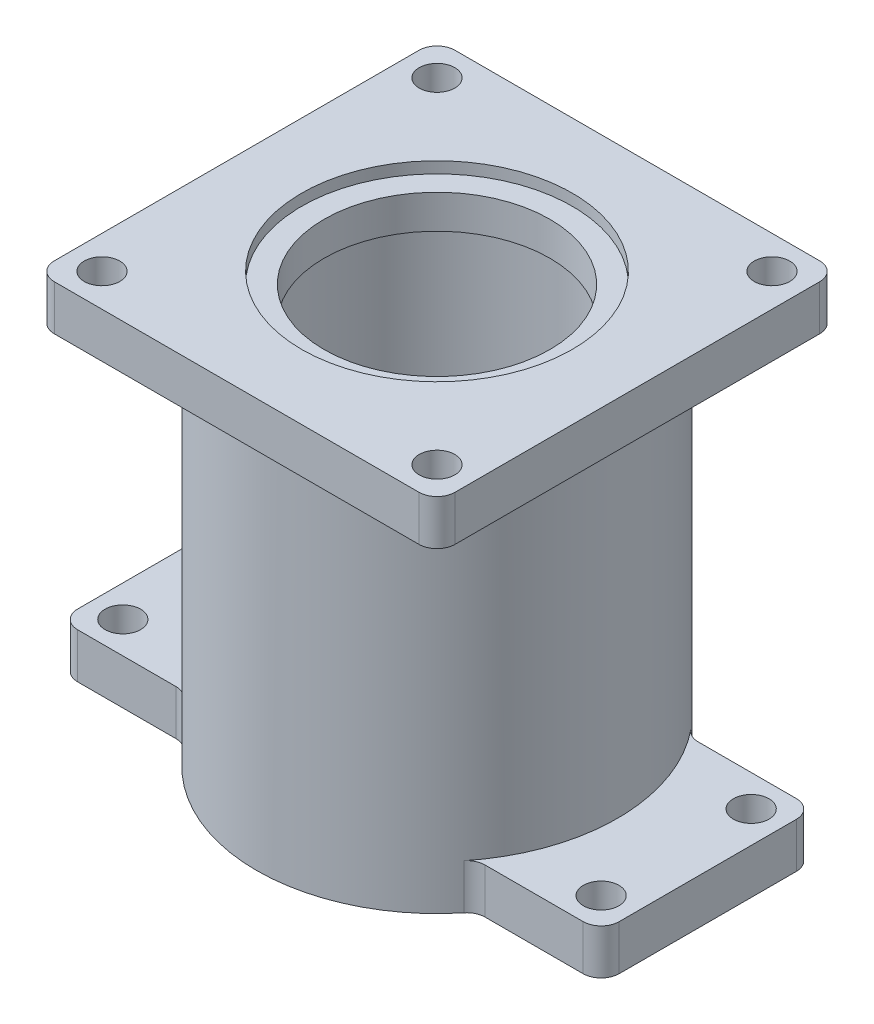
SolidWorks part; units mm, degrees
material "1060 Alloy"
ref_plane "Front Plane" through (0, 0, 0) normal (0, 0, 1) x (1, 0, 0)
ref_plane "Top Plane" through (0, 0, 0) normal (0, 1, 0) x (1, 0, 0)
ref_plane "Right Plane" through (0, 0, 0) normal (1, 0, 0) x (0, 0, -1)
sketch "Sketch2" plane through (0, 0, 0) normal (0, 1, 0) x (1, 0, 0)
  line L1 (-23.57, -23.57) -> (23.57, -23.57)
  line L2 (-23.57, -23.57) -> (-23.57, 23.57)
  line L3 (-23.57, 23.57) -> (23.57, 23.57)
  line L4 (23.57, -23.57) -> (23.57, 23.57)
  line L5 (-23.57, -23.57) -> (23.57, 23.57) construction
  line L6 (-23.57, 23.57) -> (23.57, -23.57) construction
  line L7 (28.2, -28.2) -> (-28.2, -28.2)
  line L8 (28.2, -28.2) -> (28.2, 28.2)
  line L9 (28.2, 28.2) -> (-28.2, 28.2)
  line L10 (-28.2, -28.2) -> (-28.2, 28.2)
  line L11 (28.2, -28.2) -> (-28.2, 28.2) construction
  line L12 (28.2, 28.2) -> (-28.2, -28.2) construction
  circle A0 centre (0, 0) radius 19.05
  circle A1 centre (0, 0) radius 15.8877
  circle A2 centre (23.57, 23.57) radius 2.5
  circle A3 centre (23.57, -23.57) radius 2.5
  circle A4 centre (-23.57, -23.57) radius 2.5
  circle A5 centre (-23.57, 23.57) radius 2.5
  point P21 (0, 0)
  dimension "D1" = 31.7754
  dimension "D2" = 38.1
  dimension "D6" = 5
  dimension "D3" = 47.14
  dimension "D4" = 56.4
  dimension "D5" = 4
extrude "Boss-Extrude1" add sketch "Sketch2" against normal blind 6.35 contours A0 A1 | A5 L2 A4 L1 A3 L4 A2 L3 A0 | L10 L7 L8 L9 A5 L3 A2 L4 A3 L1 A4 L2 region at (-21.3308, 0, 21.3308) region at (0, 0, 27.4024) region at (-18.5112, 0, 0)
extrude "Cut-Extrude2" cut sketch "Sketch2<4>" against normal blind 1.6 contours A0 A1 region at (-18.5112, 0, 0)
sketch "Sketch2<4>" plane through (0, 0, 0) normal (0, 1, 0) x (1, 0, 0) same geometry as "Sketch2"
sketch "Sketch3" plane through (0, -6.35, 0) normal (0, -1, 0) x (1, 0, 0)
  circle A0 centre (0, 0) radius 19.05
  circle A1 centre (0, 0) radius 25.4
  dimension "D1" = 6.35
extrude "Boss-Extrude2" add sketch "Sketch3" along normal blind 47.625
sketch "Sketch4" plane through (0, -53.975, 0) normal (0, -1, 0) x (1, 0, 0)
  line L0 (-33.655, 10.555) -> (-33.655, -10.555)
  line L1 (-38.1, 15) -> (38.1, 15)
  line L2 (-38.1, 15) -> (-38.1, -15)
  line L3 (-38.1, -15) -> (38.1, -15)
  line L4 (38.1, 15) -> (38.1, -15)
  line L5 (-38.1, 15) -> (38.1, -15) construction
  line L6 (-38.1, -15) -> (38.1, 15) construction
  line L7 (-33.655, -10.555) -> (33.655, -10.555)
  line L8 (33.655, 10.555) -> (33.655, -10.555)
  line L9 (-33.655, 10.555) -> (33.655, 10.555)
  circle A0 centre (0, 0) radius 25.4
  circle A1 centre (-33.655, 10.555) radius 2.5
  circle A2 centre (33.655, 10.555) radius 2.5
  circle A3 centre (33.655, -10.555) radius 2.5
  circle A4 centre (-33.655, -10.555) radius 2.5
  circle A5 centre (0, 0) radius 7.62
  point P0 (0, 0)
  circle M6 centre (0, 0) radius 25.4
  circle M7 centre (0, 0) radius 19.05
  dimension "D4" = 5
  dimension "D5" = 15.24
  dimension "D1" = 30
  dimension "D2" = 76.2
  dimension "D3" = 4.445
extrude "Boss-Extrude3" add sketch "Sketch4" along normal blind 6.35 contours A3 L8 A2 L9 L7 M6 | L9 L7 M7 | L9 L7 M7 M6 | L9 L7 M6 M7 | A4 L7 L9 A1 L0 M6 | A4 L0 A1 L9 L1 L2 L3 L7 M6 | A3 L7 L3 L4 L1 L9 A2 L8 M6 | L7 L3 M7 | L9 L1 M7 | L9 L1 M7 M6 | L9 L1 M6 M7 | L7 L3 M6 M7 | L7 L3 M7 M6 | A0 | A5 region at (-28.9374, -53.975, 0) region at (-34.0028, -53.975, 0) region at (-17.9089, -53.975, 12.847) region at (-21.3051, -53.975, 0) region at (0, -53.975, 12.6698) region at (0, -53.975, 10.1194) region at (-17.9089, -53.975, -12.847) region at (17.9089, -53.975, 12.847) region at (21.3051, -53.975, 0) region at (0, -53.975, -12.6698) region at (29.2989, -53.975, 14.6522) region at (28.9374, -53.975, 0) region at (17.9089, -53.975, -12.847)
fillet "Fillet1" radius 2.54 12 edges at (20.4978, -57.15, -15) (-20.4978, -57.15, -15) (-20.4978, -57.15, 15) (20.4978, -57.15, 15) (-28.2, -3.175, -28.2) (28.2, -3.175, -28.2) (28.2, -3.175, 28.2) (-28.2, -3.175, 28.2) (-38.1, -57.15, 15) (-38.1, -57.15, -15) (38.1, -57.15, -15) (38.1, -57.15, 15)
equation "\"t\"= 6.35mm"
equation "\"hole_dis\"= 47.14mm"
equation "\"outer_dis\"= 56.4mm"
equation "\"center_di\"= 1.25 + .001"
equation "\"inset\"= 38.1mm"
equation "\"h\"= 1.6mm"
equation "\"screw\"= 5mm"
equation "\"L\"= 1 + ( 7 / 8 )"
equation "\"D1@Sketch2\"=\"center_di\""
equation "\"D2@Sketch2\"=\"inset\""
equation "\"D3@Sketch2\"=\"hole_dis\""
equation "\"D4@Sketch2\"=\"outer_dis\""
equation "\"D6@Sketch2\"=\"screw\""
equation "\"D1@Boss-Extrude1\"=\"t\""
equation "\"D1@Cut-Extrude2\"=\"h\""
equation "\"D1@Boss-Extrude2\"=\"L\""
equation "\"D1@Sketch4\"=\"w\""
equation "\"D1@Boss-Extrude3\"=\"t\""
equation "\"w\"= .03m"
